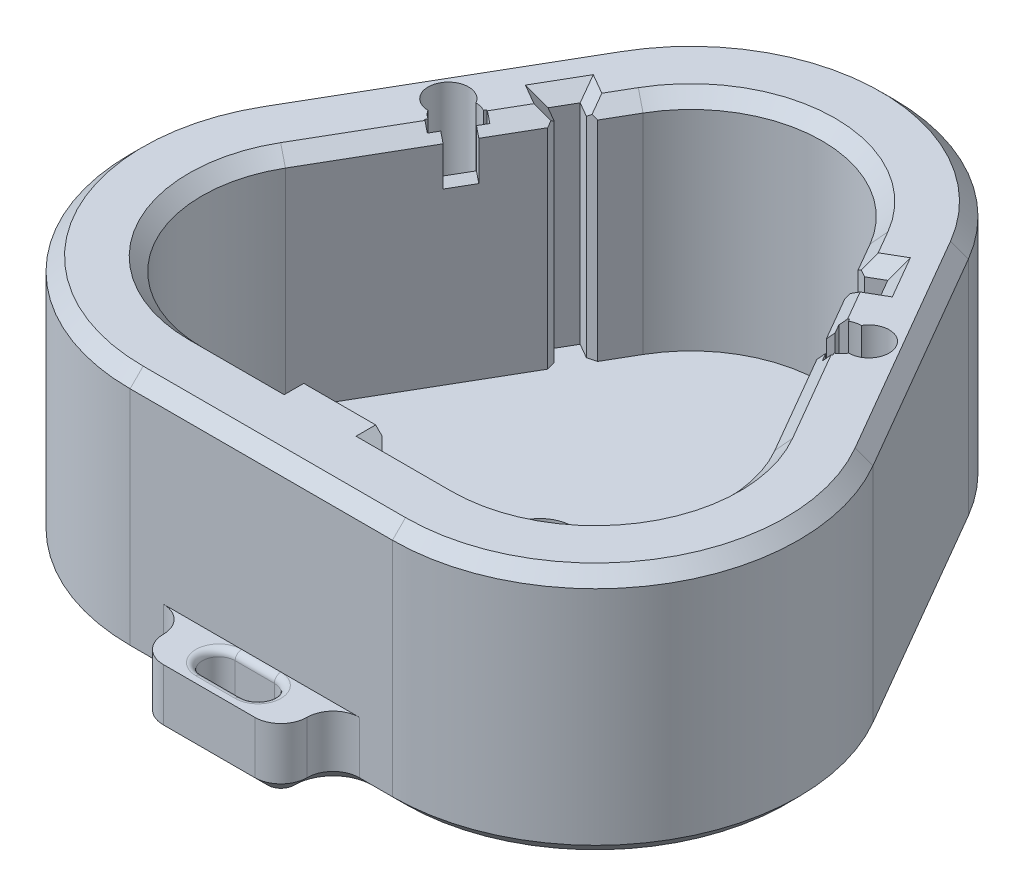
SolidWorks part; units mm, degrees
ref_plane "Front Plane" through (0, 0, 0) normal (0, 0, 1) x (1, 0, 0)
ref_plane "Top Plane" through (0, 0, 0) normal (0, 1, 0) x (1, 0, 0)
ref_plane "Right Plane" through (0, 0, 0) normal (1, 0, 0) x (0, 0, -1)
sketch "Sketch1" plane through (0, 0, 0) normal (0, 1, 0) x (1, 0, 0)
  line L0 (0, 11.5518) -> (-10.0362, -5.7759) construction
  line L1 (-10.0362, -5.7759) -> (10.0362, -5.7759) construction
  line L2 (10.0362, -5.7759) -> (0, 11.5518) construction
  line L3 (-10.0362, -5.7759) -> (5.0181, 2.8879) construction
  line L4 (-5.0181, 2.8879) -> (10.0362, -5.7759) construction
  line L5 (-8.6846, 16.5819) -> (-18.7208, -0.7458)
  line L6 (-10.0362, -15.8121) -> (10.0362, -15.8121)
  line L7 (8.6846, 16.5819) -> (18.7208, -0.7458)
  line L8 (0, 21.5879) -> (0, -15.8121) construction
  line L9 (-13.4439, 19.3385) -> (-23.4801, 2.0108)
  line L10 (-10.0362, -21.3121) -> (10.0362, -21.3121)
  line L11 (13.4439, 19.3385) -> (23.4801, 2.0108)
  line L25 (-3.75, -15.3121) -> (3.75, -15.3121)
  line L26 (-3.75, -15.8121) -> (-3.75, -15.3121)
  line L27 (3.75, -15.3121) -> (3.75, -15.8121)
  line L28 (0, -15.2648) -> (0, -15.7648) construction
  line L29 (-3.75, -15.8121) -> (3.75, -15.8121)
  line L34 (8.6846, 16.5819) -> (18.7208, -0.7458) construction
  line L35 (-8.6846, 16.5819) -> (-18.7208, -0.7458) construction
  line L36 (-10.2087, 13.9505) -> (-11.7663, 14.8527)
  line L37 (-11.7663, 14.8527) -> (-12.6685, 13.2951)
  line L38 (-12.6685, 13.2951) -> (-11.1109, 12.3929)
  line L39 (-11.1109, 12.3929) -> (-10.2087, 13.9505)
  line L40 (10.2087, 13.9505) -> (11.7663, 14.8527)
  line L41 (11.7663, 14.8527) -> (12.6685, 13.2951)
  line L42 (12.6685, 13.2951) -> (11.1109, 12.3929)
  line L43 (-13.3501, 9.5244) -> (-15.1043, 6.4957)
  line L44 (-15.1043, 6.4957) -> (-15.6235, 6.7965)
  line L45 (-15.6235, 6.7965) -> (-13.8693, 9.8251)
  line L46 (-13.8693, 9.8251) -> (-13.3501, 9.5244)
  line L47 (13.8693, 9.8251) -> (13.3501, 9.5244)
  line L48 (15.1043, 6.4957) -> (15.6235, 6.7965)
  line L49 (15.6235, 6.7965) -> (13.8693, 9.8251)
  line L50 (13.3501, 9.5244) -> (15.1043, 6.4957)
  arc A1 (-18.7208, -0.7458) -> (-10.0362, -15.8121) centre (-10.0362, -5.7759) ccw
  arc A2 (10.0362, -15.8121) -> (18.7208, -0.7458) centre (10.0362, -5.7759) ccw
  arc A5 (8.6846, 16.5819) -> (-8.6846, 16.5819) centre (0, 11.5518) ccw
  arc A6 (13.4439, 19.3385) -> (-13.4439, 19.3385) centre (0, 11.5518) ccw
  arc A7 (-23.4801, 2.0108) -> (-10.0362, -21.3121) centre (-10.0362, -5.7759) ccw
  arc A8 (10.0362, -21.3121) -> (23.4801, 2.0108) centre (10.0362, -5.7759) ccw
  arc A9 (-13.9696, 9.6521) -> (-15.5233, 6.9695) centre (-14.7464, 8.3108) ccw
  arc A10 (13.9696, 9.6521) -> (15.5233, 6.9695) centre (14.7464, 8.3108) cw
  circle A11 centre (-16.0877, 9.0877) radius 1.55
  circle A12 centre (16.0877, 9.0877) radius 1.55
  point P5 (0, 21.5879)
  point P7 (0, 0)
  point P28 (0, -15.3121)
  point P50 (0, 0)
  dimension "D1" = 37.4
  dimension "D2" = 5.5
  dimension "D8" = 3.1
  dimension "D3" = 3.5
  dimension "D4" = 20.0723
  dimension "D5" = 1.8
  dimension "D7" = 3.0409
  dimension "D9" = 0.6
  dimension "D10" = 0.5
  dimension "D11" = 0.5
  dimension "D12" = 5.3545
  dimension "D6" = 7.5
extrude "Boss-Extrude1" add sketch "Sketch1" along normal blind 17 contours L10 A8 L11 A6 L9 A7 A9 L45 L46 L43 L44 A5 L7 L40 L41 L42 A2 L6 A1 L5 L38 L37 L36 L49 A10 L48 L50 L47 | L27 L25 L26 L6 region at (0, 0, 15.5621) region at (0, 0, -26.3838)
chamfer "Chamfer1" distance 0.5 angle 45 4 edges at (10.2087, 8.5, -13.9505) (-10.2087, 8.5, -13.9505) (11.1109, 8.5, -12.3929) (-11.1109, 8.5, -12.3929) tangent propagation no
extrude "Boss-Extrude2" add sketch "Sketch1<4>" against normal blind 2 contours A9 A11 | A11 A9 | A10 A12 | A10 A12 | L11 A8 L10 A7 L9 A6 region at (-15.4171, 0, -8.6992) region at (-16.5183, 0, -9.337) region at (15.4171, 0, -8.6992) region at (16.5183, 0, -9.337)
sketch "Sketch1<4>" plane through (0, 0, 0) normal (0, 1, 0) x (1, 0, 0) same geometry as "Sketch1"
sketch "Sketch2" plane through (0, -2, 0) normal (0, -1, 0) x (1, 0, 0)
  line L0 (5.5, 21.3121) -> (5.5, 25.3121)
  line L5 (5.5, 25.3121) -> (-5.5, 25.3121)
  line L6 (-5.5, 25.3121) -> (-5.5, 21.3121)
  line L7 (-5.5, 21.3121) -> (5.5, 21.3121)
  line L8 (-1.5, 23.0621) -> (1.5, 23.0621) construction
  line L9 (-1.5, 24.3121) -> (1.5, 24.3121)
  line L10 (-1.5, 21.8121) -> (1.5, 21.8121)
  line L11 (-10.0362, 21.3121) -> (10.0362, 21.3121) construction
  arc A6 (-1.5, 24.3121) -> (-1.5, 21.8121) centre (-1.5, 23.0621) ccw
  arc A7 (1.5, 21.8121) -> (1.5, 24.3121) centre (1.5, 23.0621) ccw
  circle A8 centre (0, 0) radius 2.5
  point P2 (0, 21.3121)
  point P18 (0, 25.3121)
  point P21 (0, 23.0621)
  dimension "D4" = 5.5
  dimension "D6" = 5
  dimension "D1" = 11
  dimension "D2" = 4
  dimension "D3" = 2.5
  dimension "D5" = 0.5
extrude "Cut-Extrude2" cut sketch "Sketch2" against normal up to next contours A8 region at (0, -2, 0)
extrude "Boss-Extrude3" add sketch "Sketch2<2>" against normal blind 5 contours L5 L6 L0 A7 L10 A6 L9 region at (0, -2, 21.4291)
sketch "Sketch2<2>" plane through (0, -2, 0) normal (0, -1, 0) x (1, 0, 0) same geometry as "Sketch2"
fillet "Fillet1" radius 2 4 edges at (5.5, 0.5, 21.3121) (5.5, 0.5, 25.3121) (-5.5, 0.5, 25.3121) (-5.5, 0.5, 21.3121)
fillet "Fillet2" radius 0.5 4 edges at (0, 3, 24.3121) (2.75, 3, 23.0621) (0, 3, 21.8121) (-2.75, 3, 23.0621)
chamfer "Chamfer4" distance 1 angle 45 18 edges at (0, -2, 25.3121) (18.462, 17, -10.6747) (0, 17, -27.0879) (23.4963, 17, 13.5346) (-18.462, 17, -10.6747) (0, 17, 21.3121) (-23.4963, 17, 13.5346) (6.0858, -2, 21.8978) (8.7681, -2, 21.3121) (4.9142, -2, 24.7263) (23.4963, -2, 13.5346) (18.462, -2, -10.6747) (-4.9142, -2, 24.7263) (0, -2, -27.0879) (-6.0858, -2, 21.8978) (-18.462, -2, -10.6747) (-8.7681, -2, 21.3121) (-23.4963, -2, 13.5346)
sketch "Sketch3" plane through (0, 17, 0) normal (0, 1, 0) x (1, 0, 0)
  line L0 (-13.726, 8.8754) -> (-13.2934, 8.6248)
  line L2 (-13.2934, 8.6248) -> (-14.2958, 6.8941)
  line L3 (-11.3615, 11.9602) -> (-18.7208, -0.7458) construction
  line L4 (-14.2958, 6.8941) -> (-14.7284, 7.1447)
  line L5 (-14.7284, 7.1447) -> (-13.726, 8.8754)
  line L6 (-13.3501, 9.5244) -> (-15.1043, 6.4957) construction
  line L7 (0, -10.45) -> (0, 10.45) construction
  line L8 (14.7284, 7.1447) -> (13.726, 8.8754)
  line L9 (14.2958, 6.8941) -> (14.7284, 7.1447)
  line L10 (13.2934, 8.6248) -> (14.2958, 6.8941)
  line L11 (13.726, 8.8754) -> (13.2934, 8.6248)
  line L12 (-11.3615, 11.9602) -> (-18.7208, -0.7458) construction
  point P10 (-14.2272, 8.0101)
  dimension "D1" = 2
extrude "Cut-Extrude3" cut sketch "Sketch3" against normal blind 3
chamfer "Chamfer5" distance 1 angle 45 21 edges at (13.7946, 14, -7.7595) (-13.7946, 14, -7.7595) (11.2039, 17, -14.5269) (12.2174, 17, -14.0739) (12.106, 17, -12.9693) (12.3274, 17, -10.2925) (16.5083, 17, -3.0742) (18.7312, 17, 10.7879) (6.8931, 17, 15.8121) (3.75, 17, 15.5621) (-3.75, 17, 15.5621) (-6.8931, 17, 15.8121) (-18.7312, 17, 10.7879) (-16.5083, 17, -3.0742) (-12.3274, 17, -10.2925) (-12.106, 17, -12.9693) (-11.2039, 17, -14.5269) (-12.2174, 17, -14.0739) (9.3214, 17, -15.4825) (-9.3214, 17, -15.4825) (0, 17, -21.5879)
chamfer "Chamfer6" distance 0.5 angle 45 2 edges at (3.75, 8, 15.3121) (-3.75, 8, 15.3121)
